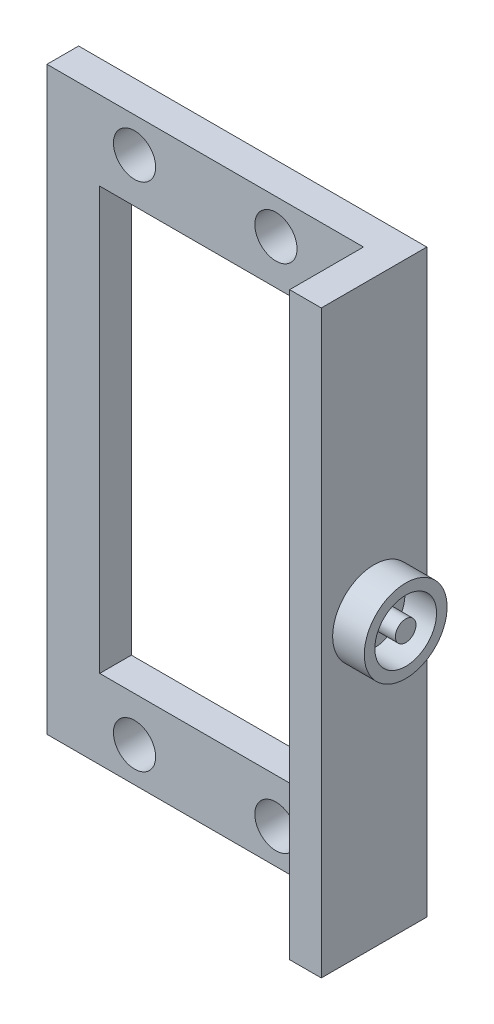
SolidWorks part; units mm, degrees
ref_plane "Front Plane" through (0, 0, 0) normal (0, 0, 1) x (1, 0, 0)
ref_plane "Top Plane" through (0, 0, 0) normal (0, 1, 0) x (1, 0, 0)
ref_plane "Right Plane" through (0, 0, 0) normal (1, 0, 0) x (0, 0, -1)
sketch "Sketch1" plane through (0, 0, 0) normal (0, 0, 1) x (1, 0, 0)
  line L9 (-10, 0) -> (10, 0)
  line L10 (-10, 0) -> (-10, 40)
  line L11 (-10, 40) -> (10, 40)
  line L12 (10, 0) -> (10, 40)
  line L17 (-15, -7.5) -> (15, -7.5)
  line L18 (-15, -7.5) -> (-15, 47.5)
  line L19 (-15, 47.5) -> (15, 47.5)
  line L20 (15, -7.5) -> (15, 47.5)
  point P4 (0, 0)
  dimension "D1" = 20
  dimension "D2" = 40
  dimension "D4" = 5
  dimension "D5" = 7.5
  dimension "D3" = 5
  dimension "D6" = 7.5
extrude "Servo Mount" add sketch "Sketch1" along normal blind 3
hole_wizard "Ø4.0 (4) Diameter Hole1" positions "Sketch2" profile "Sketch3" hole size "Ø4.0" standard "ANSI Metric"
sketch "Sketch2" plane through (0, 0, 3) normal (0, 0, 1) x (1, 0, 0)
  line L1 (-6.7, 44.2) -> (6.7, 44.2) construction
  line L2 (-6.7, 44.2) -> (-6.7, -4.2) construction
  line L3 (-6.7, -4.2) -> (6.7, -4.2) construction
  line L4 (6.7, 44.2) -> (6.7, -4.2) construction
  line L5 (-15, 47.5) -> (-15, -7.5) construction
  line L7 (-15, 20) -> (15, 20) construction
  line L8 (15, -7.5) -> (15, 47.5) construction
  line L10 (0, 47.5) -> (0, -7.5) construction
  line L11 (15, 47.5) -> (-15, 47.5) construction
  line L12 (-15, -7.5) -> (15, -7.5) construction
  line L13 (-10, 40) -> (-10, 0) construction
  point P0 (-6.7, 44.2)
  point P2 (-6.7, -4.2)
  point P4 (6.7, 44.2)
  point P6 (6.7, -4.2)
  point P96 (-6.7, 20)
  point P97 (0, -4.2)
  dimension "D1" = 3.3
  dimension "D2" = 3.3
sketch "Sketch3" plane through (-6.7, 44.2, 3) normal (1, 0, 0) x (0, -1, 0)
  line L0 (0, 0) -> (0, 5.2017)
  line L1 (0, 5.2017) -> (2, 4)
  line L2 (2, 4) -> (2, 0)
  line L5 (2, 0) -> (0, 0)
  line L10 (0, 5.2017) -> (-2, 4) construction
  line L11 (0, -6.35) -> (0, 107.95) construction
  dimension "Hole Dia." = 4
  dimension "Hole Depth" = 4
  dimension "Drill Angle" = 118
sketch "Sketch4" plane through (15, 0, 0) normal (1, 0, 0) x (0, 0, -1)
  line L0 (-3, -7.5) -> (0, -7.5) construction
  line L1 (0, -7.5) -> (-10, -7.5)
  line L2 (0, -7.5) -> (0, 47.5)
  line L3 (0, 47.5) -> (-10, 47.5)
  line L4 (-10, -7.5) -> (-10, 47.5)
  line L5 (-3, 47.5) -> (0, 47.5) construction
  line L6 (-5, -7.5) -> (-5, 47.5) construction
  line L7 (-10, 20) -> (0, 20) construction
  line L8 (0, -7.5) -> (0, 47.5) construction
  circle A0 centre (-5, 20) radius 2.925
  circle A1 centre (-5, 20) radius 0.975
  circle A3 centre (-5, 20) radius 3.925
  line M13 (-3, 47.5) -> (-3, -7.5)
  dimension "D1" = 1.95
  dimension "D2" = 5.85
  dimension "D4" = 10
  dimension "D3" = 1
extrude "Axle Mount Base" add sketch "Sketch4" along normal blind 3 contours L4 L3 L2 L1
extrude "Axle Mount" add sketch "Sketch4<3>" along normal blind 3 from surface contours A3 A0 M13 | A3 A0 M13 | A1 region at (15, 20, 2.037) region at (15, 20, 8.8266) starting at face at (18, 20, 5)
sketch "Sketch4<3>" plane through (15, 0, 0) normal (1, 0, 0) x (0, 0, -1) same geometry as "Sketch4"
equation "\"D3@Sketch1\"=\"D4@Sketch1\""
equation "\"D6@Sketch1\"=\"D5@Sketch1\""
equation "\"D1@Sketch4\"=1.85 + 0.1"
equation "\"D2@Sketch4\"=5.75+0.1"
